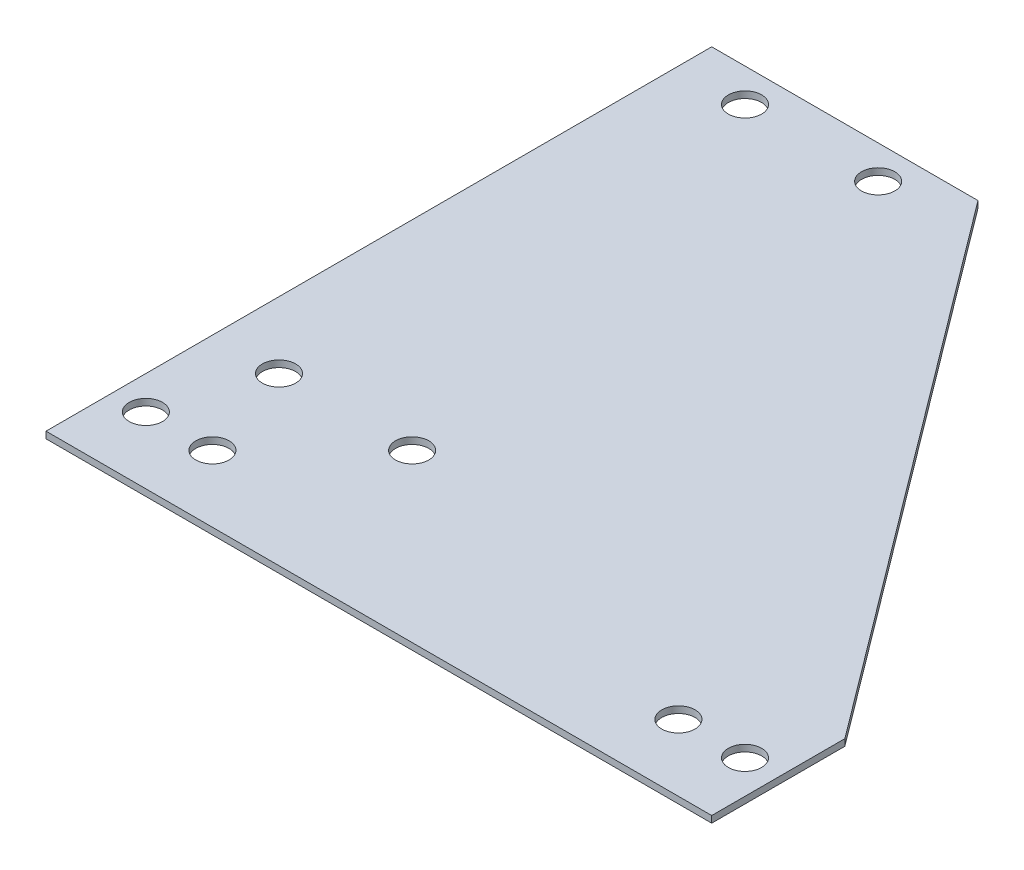
SolidWorks part; units mm, degrees
ref_plane "Front Plane" through (0, 0, 0) normal (0, 0, 1) x (1, 0, 0)
ref_plane "Top Plane" through (0, 0, 0) normal (0, 1, 0) x (1, 0, 0)
ref_plane "Right Plane" through (0, 0, 0) normal (1, 0, 0) x (0, 0, -1)
sketch "Sketch1" plane through (0, 0, 0) normal (0, 1, 0) x (1, 0, 0)
  line L0 (0, 0) -> (0, -100)
  line L1 (0, -100) -> (100, -100)
  line L2 (100, -100) -> (100, -80)
  line L3 (100, -80) -> (40, 0)
  line L4 (40, 0) -> (0, 0)
  line L5 (40, 0) -> (40, -80) construction
  line L6 (40, -80) -> (100, -80) construction
  line L7 (40, -5) -> (20, -5) construction
  line L8 (20, -5) -> (0, -5) construction
  line L9 (40, -40) -> (0, -40) construction
  line L10 (50, -80) -> (50, -100) construction
  circle A0 centre (10, -5) radius 2.5
  circle A1 centre (30, -5) radius 2.5
  circle A2 centre (85, -90) radius 2.5
  circle A3 centre (95, -90) radius 2.5
  circle A6 centre (30, -75) radius 2.5
  circle A7 centre (10, -75) radius 2.5
  circle A8 centre (5, -90) radius 2.5
  circle A9 centre (15, -90) radius 2.5
  point P19 (100, -90)
  point P31 (0, 0)
  point P32 (50, -100)
  dimension "D4" = 5
  dimension "D6" = 5
  dimension "D7" = 10
  dimension "D1" = 40
  dimension "D2" = 20
  dimension "D3" = 100
  dimension "D5" = 5
extrude "Boss-Extrude1" add sketch "Sketch1" along normal blind 1
